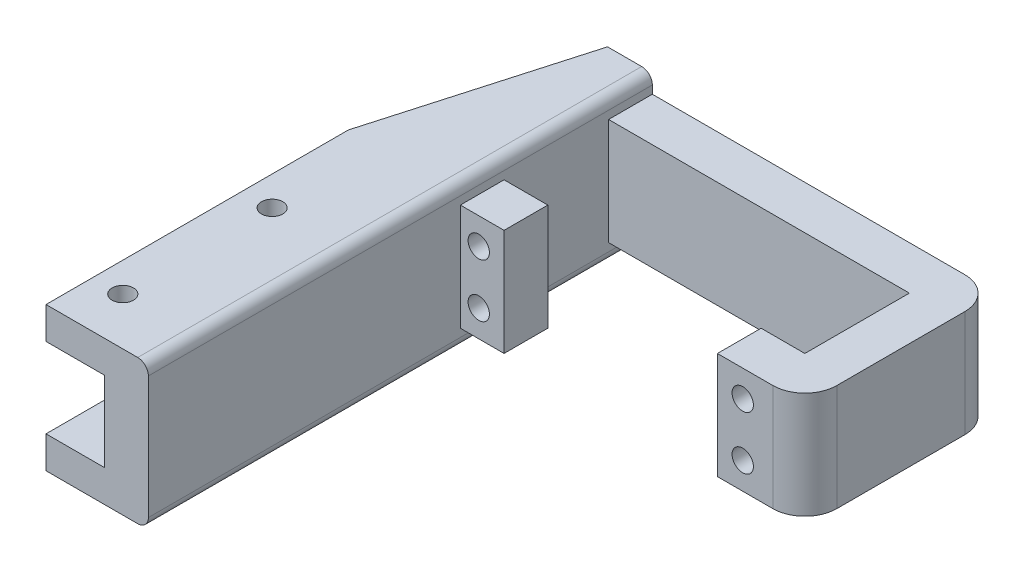
SolidWorks part; units mm, degrees
ref_plane "Piano frontale" through (0, 0, 0) normal (0, 0, 1) x (1, 0, 0)
ref_plane "Piano superiore" through (0, 0, 0) normal (0, 1, 0) x (1, 0, 0)
ref_plane "Piano destro" through (0, 0, 0) normal (1, 0, 0) x (0, 0, -1)
sketch "Schizzo1" plane through (0, 0, 0) normal (0, 0, 1) x (1, 0, 0)
  line L0 (0, 0) -> (64.6, 0)
  line L1 (64.6, 0) -> (64.6, 20)
  line L2 (64.6, 20) -> (0, 20)
  line L3 (0, 20) -> (0, 0)
  dimension "D1" = 64.6
  dimension "D2" = 20
extrude "Estrusione-Estrusione1" add sketch "Schizzo1" along normal blind 8.2
sketch "Schizzo2" plane through (0, 0, 8.2) normal (0, 0, 1) x (1, 0, 0)
  line L0 (0, 20) -> (0, 0)
  line L1 (0, 0) -> (8.2, 0)
  line L2 (0, 0) -> (64.6, 0) construction
  line L3 (8.2, 0) -> (8.2, 20)
  line L4 (64.6, 20) -> (0, 20) construction
  line L5 (8.2, 20) -> (0, 20)
  dimension "D1" = 8.2
extrude "Estrusione-Estrusione2" add sketch "Schizzo2" along normal blind 27.8
sketch "Schizzo3" plane through (0, 0, 8.2) normal (0, 0, 1) x (1, 0, 0)
  line L0 (64.6, 20) -> (64.6, 0)
  line L1 (64.6, 0) -> (56.4, 0)
  line L2 (8.2, 0) -> (64.6, 0) construction
  line L3 (56.4, 0) -> (56.4, 20)
  line L4 (64.6, 20) -> (8.2, 20) construction
  line L5 (56.4, 20) -> (64.6, 20)
  dimension "D1" = 8.2
extrude "Estrusione-Estrusione3" add sketch "Schizzo3" along normal blind 27.8
sketch "Schizzo4" plane through (56.4, 0, 0) normal (-1, 0, 0) x (0, 0, 1)
  line L0 (36, 20) -> (27.8, 20)
  line L1 (36, 20) -> (8.2, 20) construction
  line L2 (27.8, 20) -> (27.8, 0)
  line L3 (36, 0) -> (8.2, 0) construction
  line L4 (27.8, 0) -> (36, 0)
  line L5 (36, 0) -> (36, 20)
  dimension "D1" = 8.2
extrude "Estrusione-Estrusione4" add sketch "Schizzo4" along normal blind 8.2
sketch "Schizzo5" plane through (0, 0, 0) normal (-1, 0, 0) x (0, 0, 1)
  line L0 (36, 0) -> (0, 0)
  line L1 (0, 0) -> (0, 20)
  line L2 (0, 20) -> (36, 20)
  line L3 (36, 20) -> (36, 0)
extrude "Estrusione-Estrusione5" add sketch "Schizzo5" along normal blind 8.2
sketch "Schizzo6" plane through (0, 0, 0) normal (0, -1, 0) x (1, 0, 0)
  line L0 (48.2, 27.8) -> (0, 27.8)
  line L1 (0, 27.8) -> (0, 8.2)
  line L2 (0, 8.2) -> (48.2, 8.2)
  line L3 (8.2, 8.2) -> (56.4, 8.2) construction
  line L4 (48.2, 8.2) -> (48.2, 27.8)
  line L5 (8.2, 36) -> (8.2, 8.2) construction
  dimension "D1" = 8.2
extrude "Taglio-Estrusione1" cut sketch "Schizzo6" against normal through all
hole_wizard "Ø4.0 (4) Diameter Hole2" positions "Schizzo7" profile "Schizzo8" hole size "Ø4.0" standard "ISO" end condition up to next
sketch "Schizzo7" plane through (0, 0, 36) normal (0, 0, 1) x (1, 0, 0)
  line L0 (8.2, 20) -> (-8.2, 20) construction
  line L3 (64.6, 20) -> (48.2, 20) construction
  line L4 (48.2, 0) -> (48.2, 20) construction
  point P0 (52.95, 5)
  point P2 (3.45, 5)
  point P4 (3.45, 15)
  point P6 (52.95, 15)
  dimension "D1" = 10
  dimension "D2" = 10
  dimension "D3" = 49.5
  dimension "D4" = 49.5
  dimension "D5" = 5
  dimension "D6" = 0
  dimension "D7" = 4.75
  dimension "D8" = 5
sketch "Schizzo8" plane through (52.95, 5, 36) normal (1, 0, 0) x (0, -1, 0)
  line L0 (0, 0) -> (0, 8.2)
  line L1 (0, 8.2) -> (2, 8.2)
  line L2 (2, 8.2) -> (2, 0)
  line L5 (2, 0) -> (0, 0)
  line L11 (0, -6.35) -> (0, 107.95) construction
  dimension "Thru Hole Dia." = 4
  dimension "Thru Hole Depth" = 8.2
fillet "Raccordo3" radius 6 2 edges at (64.6, 10, 0) (64.6, 10, 36)
sketch "Schizzo15" plane through (0, 0, 0) normal (0, -1, 0) x (1, 0, 0)
  line L0 (0, 0) -> (0, 36)
  line L2 (-8.2, 36) -> (8.2, 36) construction
  line L3 (0, 36) -> (-8.2, 36)
  line L4 (-8.2, 36) -> (-8.2, 0)
  line L5 (-8.2, 0) -> (0, 0)
extrude "Estrusione-Estrusione7" add sketch "Schizzo15" along normal blind 3.5
sketch "Schizzo16" plane through (0, 20, 0) normal (0, 1, 0) x (1, 0, 0)
  line L0 (-8.2, 0) -> (-8.2, -36)
  line L1 (-8.2, -36) -> (0, -36)
  line L2 (8.2, -36) -> (-8.2, -36) construction
  line L3 (0, -36) -> (0, 0)
  line L4 (0, 0) -> (-8.2, 0)
extrude "Estrusione-Estrusione8" add sketch "Schizzo16" along normal blind 3.5
sketch "Schizzo17" plane through (-8.2, 0, 0) normal (-1, 0, 0) x (0, 0, 1)
  line L0 (0, 17.5) -> (36, 17.5)
  line L1 (0, 23.5) -> (0, -3.5) construction
  line L2 (36, -3.5) -> (36, 23.5) construction
  line L3 (36, 17.5) -> (36, 23.5)
  line L4 (36, 23.5) -> (0, 23.5)
  line L5 (0, 23.5) -> (0, 17.5)
  line L6 (0, 2.5) -> (36, 2.5)
  line L7 (36, 2.5) -> (36, -3.5)
  line L8 (36, -3.5) -> (0, -3.5)
  line L9 (0, -3.5) -> (0, 2.5)
  dimension "D1" = 6
  dimension "D2" = 6
extrude "Estrusione-Estrusione9" add sketch "Schizzo17" along normal blind 11 contours L6 L7 L8 L9 | L5 L0 L3 L4
fillet "Raccordo6" radius 2 2 edges at (0, -3.5, 18) (0, 23.5, 18)
sketch "Schizzo24" plane through (0, 0, 36) normal (0, 0, 1) x (1, 0, 0)
  line L0 (-2, 23.5) -> (-19.2, 23.5)
  line L1 (-19.2, 23.5) -> (-19.2, 17.5)
  line L2 (-19.2, 17.5) -> (-8.2, 17.5)
  line L3 (-8.2, 17.5) -> (-8.2, 2.5)
  line L4 (-8.2, 2.5) -> (-19.2, 2.5)
  line L5 (-19.2, 2.5) -> (-19.2, -3.5)
  line L6 (-19.2, -3.5) -> (-2, -3.5)
  line L7 (0, 21.5) -> (0, -1.5)
  arc A0 (-2, -3.5) -> (0, -1.5) centre (-2, -1.5) ccw
  arc A1 (-2, 23.5) -> (0, 21.5) centre (-2, 21.5) cw
extrude "Estrusione-Estrusione11" add sketch "Schizzo24" along normal blind 58.5
hole_wizard "Ø4.0 (4) Diameter Hole1" positions "Schizzo25" profile "Schizzo26" hole size "Ø4.0" standard "ISO" end condition through all
sketch "Schizzo25" plane through (0, -3.5, 0) normal (0, -1, 0) x (-1, 0, 0)
  line L0 (19.2, -94.5) -> (19.2, 0) construction
  line L3 (19.2, -94.5) -> (2, -94.5) construction
  point P0 (13.7, -85.6)
  point P2 (13.7, -57.6)
  dimension "D1" = 5.5
  dimension "D2" = 5.5
  dimension "D3" = 28
  dimension "D4" = 8.9
sketch "Schizzo26" plane through (-13.7, -3.5, 85.6) normal (1, 0, 0) x (0, 0, -1)
  line L0 (0, 0) -> (0, 27)
  line L1 (0, 27) -> (2, 27)
  line L2 (2, 27) -> (2, 0)
  line L5 (2, 0) -> (0, 0)
  line L11 (0, -6.35) -> (0, 107.95) construction
  dimension "Thru Hole Dia." = 4
  dimension "Thru Hole Depth" = 27
sketch "Sketch1" plane through (-19.2, 0, 0) normal (-1, 0, 0) x (0, 0, 1)
  line L0 (0, 23.5) -> (0, -3.5)
  line L1 (0, -3.5) -> (47.8, -3.5)
  line L2 (94.5, -3.5) -> (0, -3.5) construction
  line L3 (47.8, -3.5) -> (47.8, 23.5)
  line L4 (94.5, 23.5) -> (0, 23.5) construction
  line L5 (47.8, 23.5) -> (0, 23.5)
  dimension "D1" = 7.8
extrude "Cut-Extrude1" cut sketch "Sketch1" against normal up to surface (11 mm away) up to face at (-8.2, 10, 47.25)
sketch "Sketch3" plane through (-8.2, 0, 0) normal (-1, 0, 0) x (0, 0, 1)
  line L0 (47.8, 23.5) -> (47.8, -3.5)
  line L1 (47.8, -3.5) -> (37.8, -3.5)
  line L2 (0, -3.5) -> (47.8, -3.5) construction
  line L3 (37.8, -3.5) -> (37.8, 23.5)
  line L4 (47.8, 23.5) -> (0, 23.5) construction
  line L5 (37.8, 23.5) -> (47.8, 23.5)
  dimension "D1" = 10
extrude "Boss-Extrude1" add sketch "Sketch3" along normal up to surface (11 mm away) up to face at (-19.2, -0.5, 71.15)
chamfer "Chamfer1" distance 38.5 distance2 11 1 edges at (-8.2, 10, 37.8) first distance on face at (-8.2, 10, 18.9)
